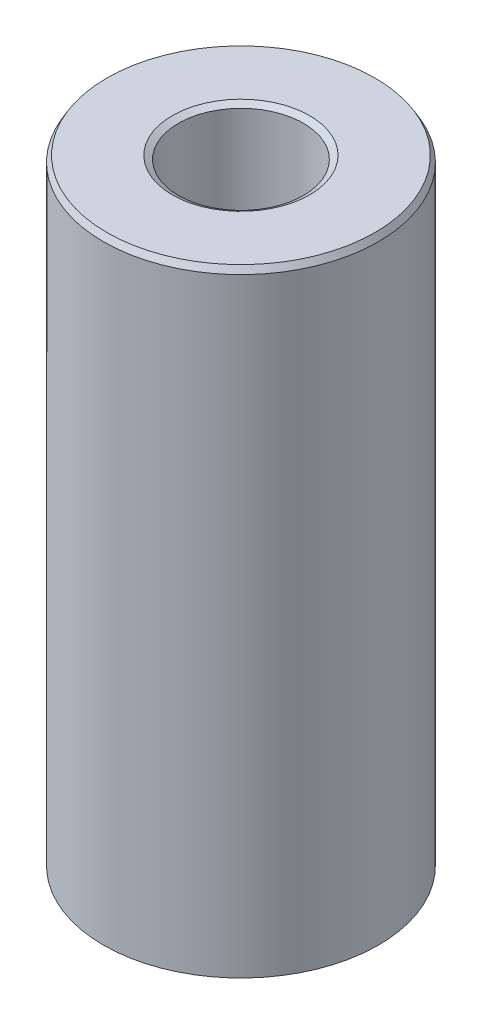
SolidWorks part; units mm, degrees
ref_plane "Front Plane" through (0, 0, 0) normal (0, 0, 1) x (1, 0, 0)
ref_plane "Top Plane" through (0, 0, 0) normal (0, 1, 0) x (1, 0, 0)
ref_plane "Right Plane" through (0, 0, 0) normal (1, 0, 0) x (0, 0, -1)
sketch "Sketch1" plane through (0, 0, 0) normal (0, 1, 0) x (1, 0, 0)
  circle A0 centre (0, 0) radius 45
  dimension "SLEEVE_OD" = 90
extrude "Boss-Extrude1" add sketch "Sketch1" along normal blind 202.5389
sketch "Sketch2" plane through (0, 0, 0) normal (0, 1, 0) x (1, 0, 0)
  circle A0 centre (0, 0) radius 20.4661
  dimension "BORE_D" = 40.9322
extrude "Cut-Extrude1" cut sketch "Sketch2" along normal through all
chamfer "Chamfer1" distance 2.0117 angle 30 4 edges at (0, 202.5389, 20.4661) (0, 0, 20.4661) (0, 0, 45) (0, 202.5389, 45) first distance on face at (0, 202.5389, 20.4661) first distance on face at (0, 0, 20.4661) first distance on face at (0, 202.5389, 45)
